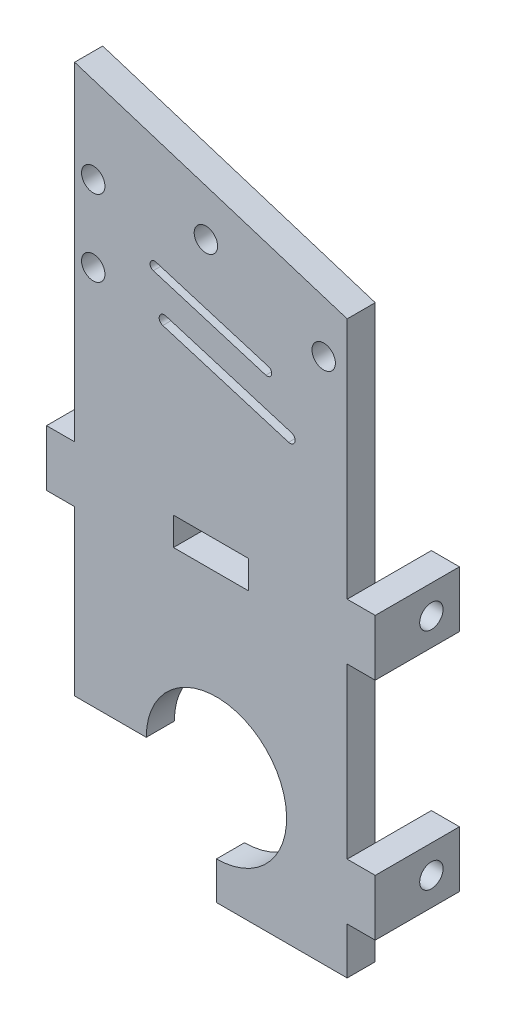
SolidWorks part; units mm, degrees
note: The reader was unsure of these and kept them because the rebuilt part matched: shared geometry of "Sketch54<3>".
ref_plane "Front Plane" through (0, 0, 0) normal (0, 0, 1) x (1, 0, 0)
ref_plane "Top Plane" through (0, 0, 0) normal (0, 1, 0) x (1, 0, 0)
ref_plane "Right Plane" through (0, 0, 0) normal (1, 0, 0) x (0, 0, -1)
sketch "Sketch1" plane through (0, 0, 0) normal (0, 1, 0) x (1, 0, 0)
  line L1 (-50.1455, -21.689) -> (-21.0155, -21.689)
  line L2 (-50.1455, -21.689) -> (-50.1455, -23.689)
  line L3 (-50.1455, -23.689) -> (-21.0155, -23.689)
  line L4 (-21.0155, -21.689) -> (-21.0155, -23.689)
extrude "Boss-Extrude1" add sketch "Sketch1" along normal blind 45.22
sketch "Sketch15" plane through (0, 0, 0) normal (0, -1, 0) x (1, 0, 0)
  line L0 (-21.0155, 23.689) -> (-28.6855, 23.689) construction
  line L1 (-28.6855, 23.689) -> (-24.8505, 23.689) construction
  line L2 (-24.8505, 23.689) -> (-24.8505, 21.689) construction
  line L4 (-24.8505, 21.689) -> (-21.0155, 21.689) construction
  line L6 (-24.8505, 23.689) -> (-21.0155, 23.689)
  line L7 (-24.8505, 23.689) -> (-24.8505, 21.689)
  line L8 (-24.8505, 21.689) -> (-21.0155, 21.689)
  line L9 (-21.0155, 23.689) -> (-21.0155, 21.689)
extrude "Boss-Extrude7" add sketch "Sketch15" along normal blind 25.02
sketch "Sketch16" plane through (0, 0, 23.689) normal (0, 0, 1) x (1, 0, 0)
  line L0 (-24.8505, 0) -> (-21.0155, -25.02) construction
  line L1 (-24.8505, 0) -> (-21.0155, -25.02)
  line L2 (-21.0155, -25.02) -> (-24.8505, -25.02)
  line L3 (-24.8505, -25.02) -> (-24.8505, 0)
extrude "Cut-Extrude5" cut sketch "Sketch16" against normal blind 4
sketch "Sketch19" plane through (-21.0155, 0, 0) normal (1, 0, 0) x (0, 0, -1)
  line L0 (-23.689, -14.02) -> (-21.689, -14.02) construction
  line L2 (-21.689, -14.02) -> (-21.689, -20.02)
  line L3 (-23.689, -20.02) -> (-21.689, -20.02)
  line L5 (-23.689, -14.02) -> (-21.689, -14.02)
  line L6 (-23.689, -14.02) -> (-23.689, -20.02)
extrude "Boss-Extrude9" add sketch "Sketch19" along normal blind 3
sketch "Sketch20" plane through (0, 0, 21.689) normal (0, 0, -1) x (-1, 0, 0)
  line L1 (18.0155, -14.02) -> (21.0155, -14.02)
  line L2 (18.0155, -14.02) -> (18.0155, -20.02)
  line L3 (18.0155, -20.02) -> (21.0155, -20.02)
  line L4 (21.0155, -14.02) -> (21.0155, -20.02)
extrude "Boss-Extrude10" add sketch "Sketch20" along normal blind 6
sketch "Sketch21" plane through (-18.0155, 0, 0) normal (1, 0, 0) x (0, 0, -1)
  circle A0 centre (-18.689, -17.012) radius 1.25
extrude "Cut-Extrude6" cut sketch "Sketch21" against normal blind 6
sketch "Sketch24" plane through (0, 0, 23.689) normal (0, 0, 1) x (1, 0, 0)
  line L0 (-21.0155, 45.22) -> (-21.0155, 37.57) construction
  line L1 (-21.0155, 45.22) -> (-21.0155, -14.02) construction
  line L2 (-21.0155, 45.22) -> (-21.0155, 37.57)
  line L3 (-21.0155, 37.57) -> (-50.1455, 45.22)
  line L4 (-50.1455, 45.22) -> (-21.0155, 45.22)
  line L5 (-21.0155, 45.22) -> (-21.0155, -14.02) construction
  line L6 (-50.1455, 45.22) -> (-21.0155, 45.22) construction
  line L8 (-21.0155, 45.22) -> (-21.0155, 37.57) construction
extrude "Cut-Extrude10" cut sketch "Sketch24" against normal blind 4
sketch "Sketch27" plane through (0, 0, 23.689) normal (0, 0, 1) x (1, 0, 0)
  circle A0 centre (-48.1555, 35.3258) radius 1.25
  circle A1 centre (-48.1555, 27.1812) radius 1.25
extrude "Cut-Extrude13" cut sketch "Sketch27" against normal blind 5
sketch "Sketch28" plane through (0, 0, 23.689) normal (0, 0, 1) x (1, 0, 0)
  line L0 (-48.1592, 35.3258) -> (-48.1592, 27.1812) construction
  line L1 (-48.1592, 27.1812) -> (-48.1592, 31.2535) construction
  line L2 (-48.1592, 31.2535) -> (-23.5255, 31.2535) construction
  circle A0 centre (-23.5255, 31.2535) radius 1.25
sketch "Sketch32" plane through (0, 0, 23.689) normal (0, 0, 1) x (1, 0, 0)
  circle A0 centre (-36.1145, 35.7898) radius 1.25
sketch "Sketch35" plane through (0, 0, 23.689) normal (0, 0, 1) x (1, 0, 0)
  line L0 (-21.0155, 37.57) -> (-21.0155, 35.99)
  line L1 (-21.0155, 37.57) -> (-21.0155, -14.02) construction
  line L2 (-21.0155, 35.99) -> (-21.0155, 37.57)
  line L3 (-21.0155, 35.99) -> (-50.1455, 45.22)
  line L4 (-50.1455, 45.22) -> (-21.0155, 37.57)
  line M5 (-21.0155, -14.02) -> (-21.0155, 37.57)
  line M6 (-21.0155, 37.57) -> (-50.1455, 45.22)
extrude "Cut-Extrude16" cut sketch "Sketch35" against normal blind 4.86 contours L3 M5 M6
sketch "Sketch36" plane through (0, 0, 23.689) normal (0, 0, 1) x (1, 0, 0)
  line L0 (-50.1455, 45.22) -> (-50.1455, 45.18) construction
  line L1 (-50.1455, 45.22) -> (-50.1455, 0) construction
  line L2 (-50.1455, 45.22) -> (-50.1455, 45.18)
  line L3 (-50.1455, 45.18) -> (-21.0155, 35.99)
  line L4 (-21.0155, 35.99) -> (-50.1455, 45.22)
extrude "Cut-Extrude17" cut sketch "Sketch36" against normal blind 4
mirror "Mirror1" about plane through (0, 0, 15.689) normal (0, 0, -1) of bodies 130
delete or keep bodies "Body-Delete/Keep 1" type delete bodies bodies 130
sketch "Sketch37" plane through (0, 0, 7.689) normal (0, 0, -1) x (-1, 0, 0)
  line L0 (21.0155, 35.99) -> (21.0155, 10.985) construction
  line L1 (21.0155, 35.99) -> (21.0155, -14.02) construction
  line L2 (21.0155, 10.985) -> (50.1455, 10.985) construction
  line L3 (50.1455, 45.18) -> (50.1455, 0) construction
  line L4 (50.1455, 10.985) -> (50.1455, 45.18) construction
  line L5 (50.1455, 45.18) -> (50.1455, 31.4195) construction
  line L6 (50.1455, 45.18) -> (21.0155, 35.99) construction
  line L7 (21.0155, 35.99) -> (21.0155, 31.4195) construction
  line L8 (21.0155, 31.4195) -> (50.1455, 40.6095) construction
  line L9 (50.1455, 40.6095) -> (50.1455, 36.0145) construction
  line L10 (50.1455, 36.0145) -> (50.1455, 40.6095) construction
  line L11 (50.1455, 40.6095) -> (21.0155, 31.4195) construction
  line L12 (21.0155, 31.4195) -> (21.0155, 24.3006) construction
  line L13 (21.0155, 24.3006) -> (50.1455, 33.1563) construction
  line L14 (29.5652, 26.8997) -> (41.5958, 30.5571) construction
  line L15 (29.4224, 27.3694) -> (41.453, 31.0268)
  line L16 (29.708, 26.4301) -> (41.7386, 30.0874)
  line L17 (21.0155, 24.3006) -> (21.0155, 20.1026) construction
  line L18 (21.0155, 20.1026) -> (50.1455, 28.9583) construction
  line L19 (27.1219, 21.959) -> (40.5639, 26.0454) construction
  line L20 (26.9639, 22.4788) -> (40.4059, 26.5653)
  line L21 (27.28, 21.4391) -> (40.722, 25.5256)
  arc A0 (29.4224, 27.3694) -> (29.708, 26.4301) centre (29.5652, 26.8997) ccw
  arc A1 (41.7386, 30.0874) -> (41.453, 31.0268) centre (41.5958, 30.5571) ccw
  arc A2 (26.9639, 22.4788) -> (27.28, 21.4391) centre (27.1219, 21.959) ccw
  arc A3 (40.722, 25.5256) -> (40.4059, 26.5653) centre (40.5639, 26.0454) ccw
  point P18 (35.5805, 28.7284)
  point P27 (33.8429, 24.0022)
extrude "Cut-Extrude20" cut sketch "Sketch37" against normal blind 15
mirror "Mirror2" about plane through (0, 0, 15.689) normal (0, 0, 1) of bodies 134
delete or keep bodies "Body-Delete/Keep 2" type delete bodies bodies 134
extrude "Cut-Extrude23" cut sketch "Sketch28" against normal blind 5 contours A0
extrude "Cut-Extrude25" cut sketch "Sketch32" against normal blind 5 contours A0
sketch "Sketch38" plane through (-50.1455, 0, 0) normal (-1, 0, 0) x (0, 0, 1)
  line L0 (23.689, 4.0427) -> (23.689, 3.98) construction
  line L1 (21.689, 4.0427) -> (23.689, 4.0427)
  line L2 (21.689, 4.0427) -> (21.689, 10.0427)
  line L3 (21.689, 10.0427) -> (23.689, 10.0427)
  line L4 (23.689, 4.0427) -> (23.689, 10.0427)
  line L5 (23.689, 45.18) -> (23.689, 0) construction
  line L6 (23.689, 10.0427) -> (23.689, 9.98) construction
extrude "Boss-Extrude11" add sketch "Sketch38" along normal blind 3
sketch "Sketch39" plane through (0, 0, 21.689) normal (0, 0, -1) x (-1, 0, 0)
  line L1 (53.1455, 10.0427) -> (50.1455, 10.0427)
  line L2 (53.1455, 10.0427) -> (53.1455, 4.0427)
  line L3 (53.1455, 4.0427) -> (50.1455, 4.0427)
  line L4 (50.1455, 10.0427) -> (50.1455, 4.0427)
extrude "Boss-Extrude12" add sketch "Sketch39" along normal blind 6
sketch "Sketch40" plane through (-53.1455, 0, 0) normal (-1, 0, 0) x (0, 0, 1)
  line L0 (15.689, 4.0427) -> (15.689, 7.0427) construction
  line L1 (15.689, 4.0427) -> (15.689, 10.0427) construction
  circle A0 centre (18.689, 6.98) radius 1.25
extrude "Cut-Extrude26" cut sketch "Sketch40" against normal blind 6
sketch "Sketch51" plane through (-21.0155, 0, 0) normal (1, 0, 0) x (0, 0, -1)
  line L0 (-23.689, 4.0427) -> (-21.689, 4.0427) construction
  line L1 (-21.689, 35.99) -> (-21.689, -14.02) construction
  line L3 (-23.689, 4.0427) -> (-21.689, 4.0427)
  line L4 (-23.689, 4.0427) -> (-23.689, 10.0427)
  line L5 (-23.689, 10.0427) -> (-21.689, 10.0427)
  line L6 (-21.689, 4.0427) -> (-21.689, 10.0427)
extrude "Boss-Extrude15" add sketch "Sketch51" along normal blind 3
sketch "Sketch52" plane through (0, 0, 21.689) normal (0, 0, -1) x (-1, 0, 0)
  line L1 (18.0155, 10.0427) -> (21.0155, 10.0427)
  line L2 (18.0155, 10.0427) -> (18.0155, 4.0427)
  line L3 (18.0155, 4.0427) -> (21.0155, 4.0427)
  line L4 (21.0155, 10.0427) -> (21.0155, 4.0427)
extrude "Boss-Extrude16" add sketch "Sketch52" along normal blind 6
sketch "Sketch53" plane through (-18.0155, 0, 0) normal (1, 0, 0) x (0, 0, -1)
  line L0 (-23.689, 7.0427) -> (-15.689, 7.0427) construction
  line L1 (-23.689, 10.0427) -> (-23.689, 4.0427) construction
  line L2 (-15.689, 10.0427) -> (-15.689, 4.0427) construction
  line L3 (-15.689, 7.0427) -> (-21.689, 7.0427) construction
  circle A0 centre (-18.689, 6.98) radius 1.25
extrude "Cut-Extrude28" cut sketch "Sketch53" against normal blind 6 contours A0
sketch "Sketch54" plane through (0, 0, 23.689) normal (0, 0, 1) x (1, 0, 0)
  line L0 (-24.8505, 0) -> (-26.3414, -1.352) construction
  line L1 (-50.1455, 0) -> (-24.8505, 0) construction
  line L2 (-37.498, 0) -> (-37.498, 7.7289) construction
  line L3 (-24.8505, 0) -> (-21.0155, -25.02) construction
  line L4 (-21.0155, -25.02) -> (-22.933, -12.51) construction
  line L5 (-22.933, -12.51) -> (-21.0155, -12.2161) construction
  line L6 (-21.0155, 4.0427) -> (-21.0155, -14.02) construction
  line L7 (-50.1455, 0) -> (-50.1455, -13.4815)
  line L8 (-50.1455, -13.4815) -> (-34.9867, -13.4815)
  line L9 (-34.9867, -13.4815) -> (-34.9867, -25.02)
  line L10 (-34.9867, -25.02) -> (-21.0155, -25.02)
  line L11 (-21.0155, -25.02) -> (-24.8505, 0)
  line L12 (-24.8505, 0) -> (-28.4755, 0)
  circle A0 centre (-34.9867, -13.4815) radius 7.5
  line M20 (-50.1455, 0) -> (-24.8505, 0)
  line M21 (-24.8505, 0) -> (-21.0155, -25.02)
extrude "Boss-Extrude17" add sketch "Sketch54" against normal blind 2 and the other way blind 1 contours A0 L7 L8 M20 | A0 M21 M20 | A0 L9 L10 M21
extrude "Cut-Extrude29" cut sketch "Sketch54<3>" against normal blind 2 and the other way blind 1 contours A0
sketch "Sketch54<3>" plane through (0, 0, 23.689) normal (0, 0, 1) x (1, 0, 0) same geometry as "Sketch54"
sketch "Sketch55" plane through (0, 0, 23.689) normal (0, 0, 1) x (1, 0, 0)
  line L0 (-50.1455, 45.18) -> (-50.1455, 10.0427)
  line L1 (-50.1455, 10.0427) -> (-53.1455, 10.0427)
  line L2 (-53.1455, 10.0427) -> (-53.1455, 4.0427)
  line L3 (-53.1455, 4.0427) -> (-50.1455, 4.0427)
  line L4 (-50.1455, 4.0427) -> (-50.1455, 0)
  line L5 (-50.1455, 0) -> (-24.8505, 0)
  line L6 (-21.0155, -25.02) -> (-24.8505, 0) construction
  line L7 (-50.1455, 0) -> (-24.8505, 0) construction
  line L8 (-24.8505, 0) -> (-21.0155, -25.02)
  line L9 (-21.0155, -25.02) -> (-21.0155, -20.02)
  line L10 (-21.0155, -20.02) -> (-18.0155, -20.02)
  line L11 (-18.0155, -20.02) -> (-18.0155, -14.02)
  line L12 (-18.0155, -14.02) -> (-21.0155, -14.02)
  line L13 (-21.0155, -14.02) -> (-21.0155, 4.0427)
  line L14 (-21.0155, 4.0427) -> (-18.0155, 4.0427)
  line L15 (-18.0155, 4.0427) -> (-18.0155, 10.0427)
  line L16 (-18.0155, 10.0427) -> (-21.0155, 10.0427)
  line L17 (-21.0155, 10.0427) -> (-21.0155, 35.99)
  line L18 (-21.0155, 35.99) -> (-50.1455, 45.18)
  line L19 (-41.5958, 30.5571) -> (-29.5652, 26.8997) construction
  line L20 (-41.4536, 31.025) -> (-29.423, 27.3676)
  line L21 (-41.738, 30.0893) -> (-29.7074, 26.4319)
  line L22 (-27.1219, 21.959) -> (-40.5639, 26.0454) construction
  line L23 (-27.2803, 21.4379) -> (-40.7223, 25.5244)
  line L24 (-26.9635, 22.48) -> (-40.4055, 26.5665)
  circle A0 centre (-23.5255, 31.2535) radius 1.25
  circle A1 centre (-36.1145, 35.7898) radius 1.25
  circle A2 centre (-48.1555, 35.3258) radius 1.25
  circle A3 centre (-48.1555, 27.1812) radius 1.25
  arc A4 (-41.4536, 31.025) -> (-41.738, 30.0893) centre (-41.5958, 30.5571) ccw
  arc A5 (-29.7074, 26.4319) -> (-29.423, 27.3676) centre (-29.5652, 26.8997) ccw
  arc A7 (-27.2803, 21.4379) -> (-26.9635, 22.48) centre (-27.1219, 21.959) ccw
  arc A8 (-40.4055, 26.5665) -> (-40.7223, 25.5244) centre (-40.5639, 26.0454) ccw
  point P50 (-35.5805, 28.7284)
  point P59 (-33.8429, 24.0022)
extrude "Boss-Extrude18" add sketch "Sketch55" along normal blind 1 and the other way blind 2
sketch "Sketch56" plane through (0, 0, 24.689) normal (0, 0, 1) x (1, 0, 0)
  line L1 (-21.0155, 10.0427) -> (-21.0155, 4.0427) construction
  line L3 (-50.1455, 4.0427) -> (-50.1455, 10.0427) construction
  line L12 (-35.5805, 8.5427) -> (-31.5805, 8.5427)
  line L13 (-31.5805, 8.5427) -> (-39.5805, 8.5427)
  line L14 (-39.5805, 8.5427) -> (-39.5805, 5.5427)
  line L15 (-39.5805, 5.5427) -> (-31.5805, 5.5427)
  line L16 (-31.5805, 5.5427) -> (-31.5805, 8.5427)
extrude "Cut-Extrude30" cut sketch "Sketch56" against normal blind 10 contours L15 L16 L12 L13 L14
